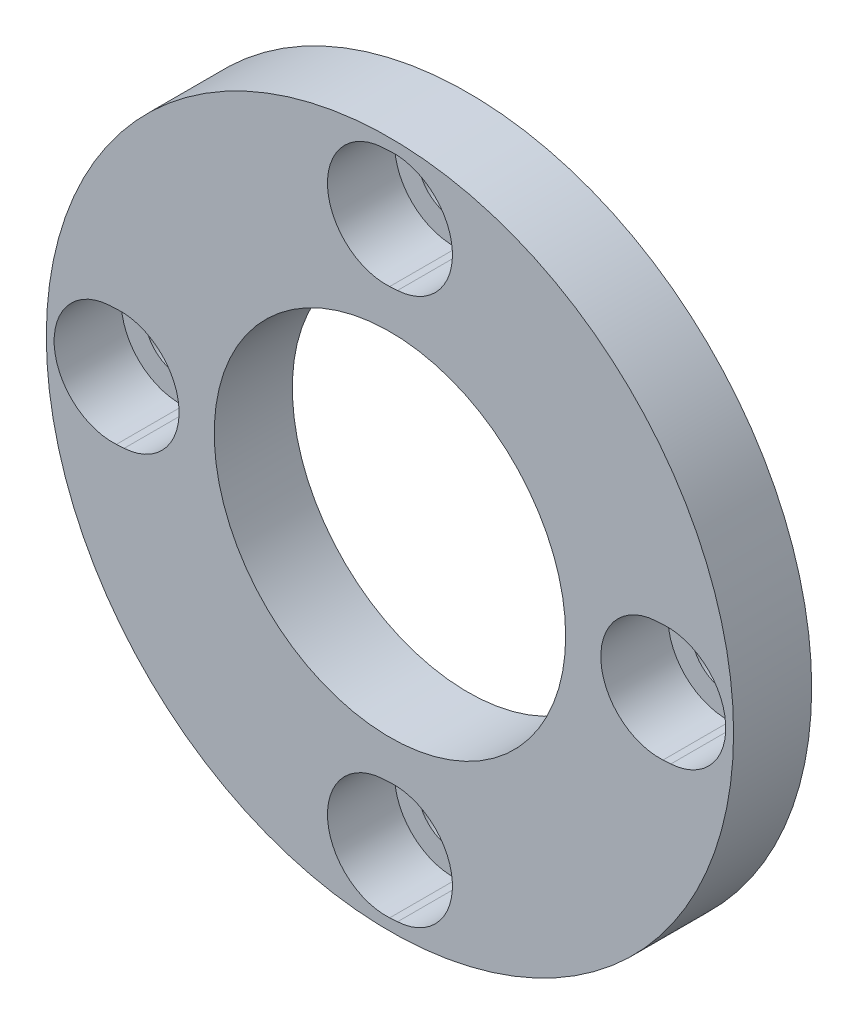
SolidWorks part; units mm, degrees
ref_plane "Front Plane" through (0, 0, 0) normal (0, 0, 1) x (1, 0, 0)
ref_plane "Top Plane" through (0, 0, 0) normal (0, 1, 0) x (1, 0, 0)
ref_plane "Right Plane" through (0, 0, 0) normal (1, 0, 0) x (0, 0, -1)
sketch "Çizim1" plane through (0, 0, 0) normal (0, 0, 1) x (1, 0, 0)
  circle A0 centre (0, 0) radius 44
  circle A1 centre (0, 0) radius 22.5
  dimension "D1" = 88
  dimension "D2" = 45
extrude "Yükseklik-Ekstrüzyon1" add sketch "Çizim1" along normal blind 10
hole_wizard "M8 Altıgen Alyan Başlı Kör Vida İçin Havşa1" positions "Çizim2" profile "Çizim3" size "M8" standard "ISO" slot yes
sketch "Çizim2" plane through (0, 0, 10) normal (0, 0, 1) x (1, 0, 0)
  line L0 (-4.9903, 34.6884) -> (4.9903, 35.3116) construction
  point P0 (0, 35)
  point P5 (35, 0)
  point P8 (0, -35)
  point P11 (-35, 0)
  point P26 (0, 35)
  dimension "D1" = 10
  dimension "D2" = 35
  dimension "D3" = 35
  dimension "D4" = 35
  dimension "D5" = 35
sketch "Çizim3" plane through (0, 35, 10) normal (1, 0, 0) x (0, -1, 0)
  line L0 (0, 0) -> (0, 24.9539)
  line L1 (0, 24.9539) -> (4.5, 22.25)
  line L2 (4.5, 22.25) -> (4.5, 8.6)
  line L3 (4.5, 8.6) -> (7.5, 8.6)
  line L4 (7.5, 8.6) -> (7.5, 0)
  line L5 (7.5, 0) -> (0, 0)
  line L10 (0, 24.9539) -> (-4.5, 22.25) construction
  line L11 (0, -6.35) -> (0, 107.95) construction
  dimension "Hole Dia." = 9
  dimension "Hole Depth" = 22.25
  dimension "C'Bore Dia." = 15
  dimension "C'Bore Depth" = 8.6
  dimension "Drill Angle" = 118
